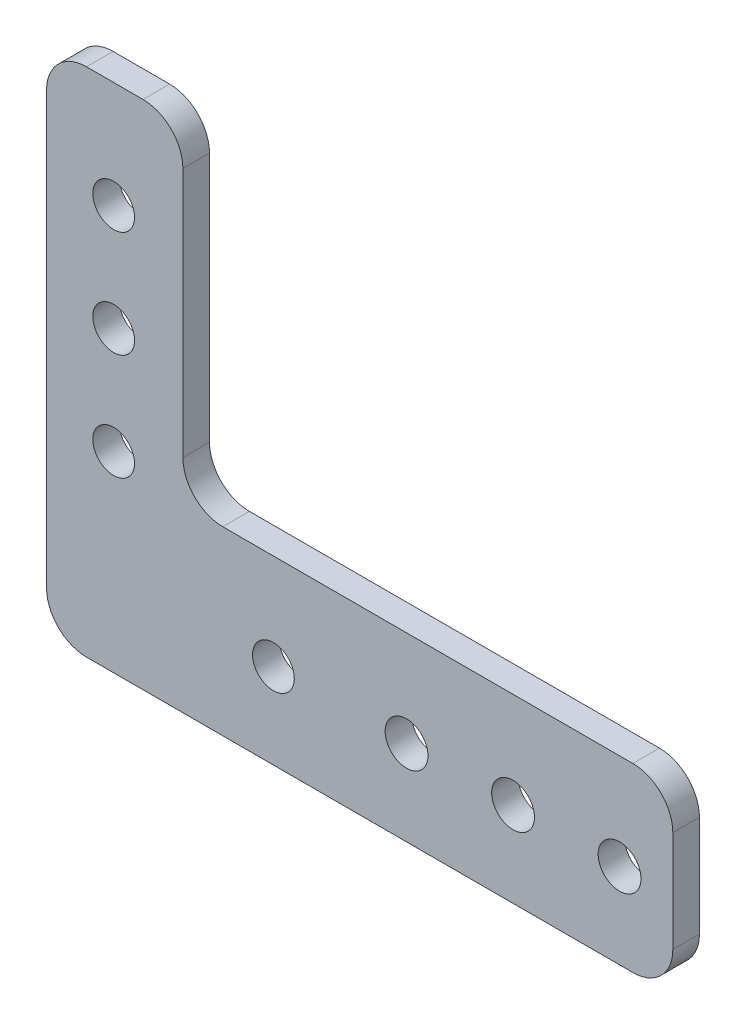
SolidWorks part; units mm, degrees
material "6061-T6 (SS)"
ref_plane "Front Plane" through (0, 0, 0) normal (0, 0, 1) x (1, 0, 0)
ref_plane "Top Plane" through (0, 0, 0) normal (0, 1, 0) x (1, 0, 0)
ref_plane "Right Plane" through (0, 0, 0) normal (1, 0, 0) x (0, 0, -1)
sketch "Sketch1" plane through (0, 0, 0) normal (0, 0, 1) x (1, 0, 0)
  line L1 (-41.275, -31.75) -> (41.275, -31.75)
  line L2 (-41.275, -31.75) -> (-41.275, 31.75)
  line L3 (-41.275, 31.75) -> (41.275, 31.75)
  line L4 (41.275, -31.75) -> (41.275, 31.75)
  line L5 (-41.275, -31.75) -> (41.275, 31.75) construction
  line L6 (-41.275, 31.75) -> (41.275, -31.75) construction
  line L7 (41.275, 31.75) -> (-17.145, 31.75)
  line L8 (41.275, 31.75) -> (41.275, -7.62)
  line L9 (41.275, -7.62) -> (-17.145, -7.62)
  line L10 (-17.145, 31.75) -> (-17.145, -7.62)
  line L11 (-41.275, -31.75) -> (-33.401, -31.75)
  line L12 (-41.275, -31.75) -> (-41.275, 31.75)
  line L13 (-41.275, 31.75) -> (-33.401, 31.75)
  line L14 (-33.401, -31.75) -> (-33.401, 31.75)
  line L15 (-33.401, -31.75) -> (41.275, -31.75)
  line L16 (-33.401, -31.75) -> (-33.401, -29.21)
  line L17 (-33.401, -29.21) -> (41.275, -29.21)
  line L18 (41.275, -31.75) -> (41.275, -29.21)
  circle A0 centre (-25.4, -19.05) radius 2.4892
  circle A1 centre (-25.4, -6.35) radius 2.4892
  circle A2 centre (-25.4, 6.35) radius 2.4892
  circle A3 centre (-25.4, 19.05) radius 2.4892
  circle A4 centre (-6.35, -19.05) radius 2.4892
  circle A5 centre (9.525, -19.05) radius 2.5527
  circle A6 centre (22.225, -19.05) radius 2.5527
  circle A7 centre (34.925, -19.05) radius 2.5527
  point P0 (0, 0)
  dimension "D7" = 4.9784
  dimension "D17" = 12.7
  dimension "D18" = 5.1054
  dimension "D1" = 82.55
  dimension "D2" = 63.5
  dimension "D3" = 24.13
  dimension "D4" = 24.13
  dimension "D5" = 7.874
  dimension "D6" = 63.5
  dimension "D8" = 15.875
  dimension "D9" = 12.7
  dimension "D10" = 12.7
  dimension "D11" = 12.7
  dimension "D12" = 12.7
  dimension "D13" = 12.7
  dimension "D14" = 27.051
  dimension "D15" = 15.875
  dimension "D16" = 2.54
extrude "Boss-Extrude1" add sketch "Sketch1" along normal blind 3.175 contours L14 L17 L4 L9 L10 L3 A6 A5 A4 A3 A2 A1 A0 | A0 region at (-4.3424, -9.7574, 0) region at (-25.4, -19.05, 0)
fillet "Fillet1" radius 4.7625 6 edges at (-33.401, 31.75, 1.5875) (-17.145, 31.75, 1.5875) (-17.145, -7.62, 1.5875) (41.275, -7.62, 1.5875) (41.275, -29.21, 1.5875) (-33.401, -29.21, 1.5875)
